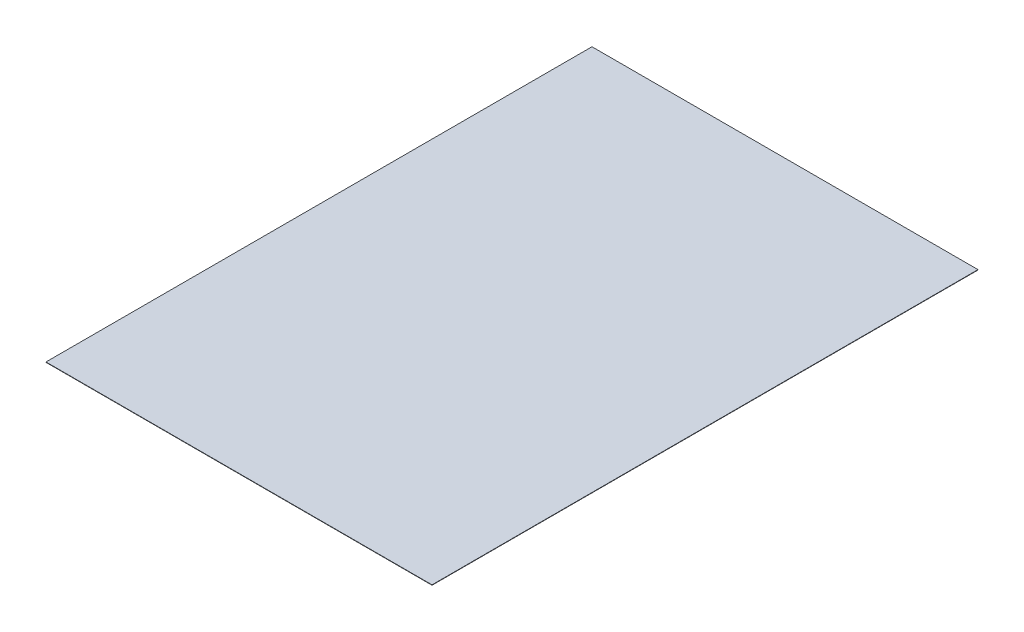
SolidWorks part; units mm, degrees
material "PE High Density"
ref_plane "Front Plane" through (0, 0, 0) normal (0, 0, 1) x (1, 0, 0)
ref_plane "Top Plane" through (0, 0, 0) normal (0, 1, 0) x (1, 0, 0)
ref_plane "Right Plane" through (0, 0, 0) normal (1, 0, 0) x (0, 0, -1)
sketch "Sketch1" plane through (0, 0, 0) normal (0, 1, 0) x (1, 0, 0)
  line L1 (0, 0) -> (210, 0)
  line L2 (0, 0) -> (0, 297)
  line L3 (0, 297) -> (210, 297)
  line L4 (210, 0) -> (210, 297)
  dimension "D1" = 210
  dimension "D2" = 297
extrude "Extrude1" add sketch "Sketch1" along normal blind 0.2
